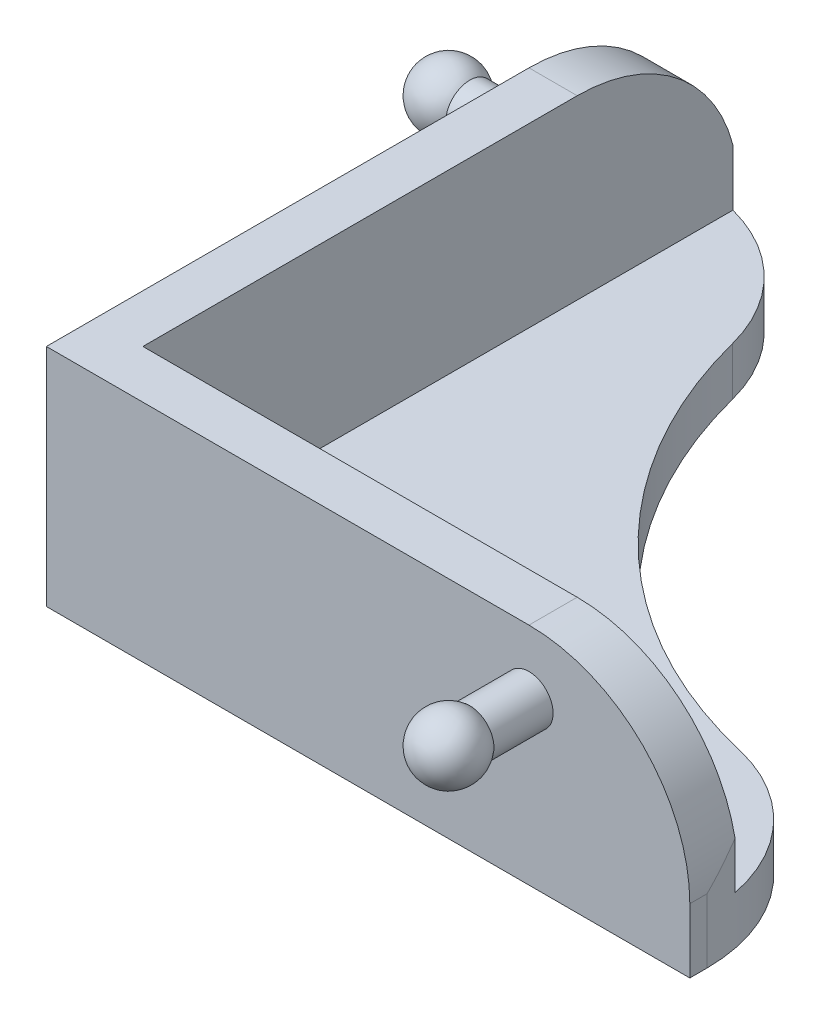
SolidWorks part; units mm, degrees
note: The reader was unsure of these and kept them because the rebuilt part matched: shared geometry of "Sketch1<4>".
ref_plane "Front Plane" through (0, 0, 0) normal (0, 0, 1) x (1, 0, 0)
ref_plane "Top Plane" through (0, 0, 0) normal (0, 1, 0) x (1, 0, 0)
ref_plane "Right Plane" through (0, 0, 0) normal (1, 0, 0) x (0, 0, -1)
sketch "Sketch1" plane through (0, 0, 0) normal (0, 1, 0) x (1, 0, 0)
  line L0 (-13.8131, -7.4977) -> (-13.8131, 29.1799)
  line L1 (-16.8131, 29.5023) -> (-16.3316, 29.5023)
  line L2 (-16.8131, 29.5023) -> (-16.8131, -10.4977)
  line L3 (-16.8131, -10.4977) -> (23.1869, -10.4977)
  line L4 (23.1869, -9.4227) -> (23.1869, -10.4977)
  line L5 (-13.8131, -7.4977) -> (22.9999, -7.4977)
  arc A0 (-6.6492, 22.0023) -> (15.4897, 0.3085) centre (22.3982, 29.5023) ccw
  arc A1 (15.4897, 0.3085) -> (23.1869, -9.4227) centre (13.1869, -9.4227) cw
  arc A2 (-6.6492, 22.0023) -> (-16.3316, 29.5023) centre (-16.3316, 19.5023) ccw
  dimension "D3" = 30
  dimension "D4" = 10
  dimension "D1" = 40
  dimension "D2" = 40
  dimension "D5" = 3
  dimension "D6" = 3
extrude "Boss-Extrude2" add sketch "Sketch1" along normal blind 3 contours A0 A2 L0 L5 A1 | L0 A2 L1 L2 L3 L4 A1 L5
extrude "Boss-Extrude3" add sketch "Sketch1<4>" along normal blind 14 contours L0 A2 L1 L2 L3 L4 A1 L5
sketch "Sketch1<4>" plane through (0, 0, 0) normal (0, 1, 0) x (1, 0, 0) same geometry as "Sketch1"
fillet "Fillet2" radius 10 2 edges at (-16.5724, 14, -29.5023) (23.1869, 14, 9.9602)
sketch "Sketch2" plane through (0, 0, 10.4977) normal (0, 0, 1) x (1, 0, 0)
  line L0 (-16.8131, 14) -> (-16.8131, 0) construction
  line L1 (22, 0) -> (-22, 0) construction
  circle A0 centre (13.1869, 10) radius 1.5
  point P4 (0, 0)
  dimension "D3" = 3
  dimension "D1" = 30
  dimension "D2" = 10
sketch "Sketch3" plane through (-16.8131, 0, 0) normal (-1, 0, 0) x (0, 0, 1)
  line L0 (10.4977, 14) -> (10.4977, 0) construction
  line L1 (22, 0) -> (-22, 0) construction
  circle A0 centre (-19.5023, 10) radius 1.5
  point P4 (0, 0)
  dimension "D3" = 3
  dimension "D1" = 30
  dimension "D2" = 10
extrude "Boss-Extrude4" add sketch "Sketch3" along normal blind 5
sketch "Sketch4" plane through (-21.8131, 0, 0) normal (-1, 0, 0) x (0, 0, 1)
  line L0 (-19.5023, 12) -> (-19.5023, 8)
  arc A0 (-19.5023, 12) -> (-19.5023, 8) centre (-19.5023, 10) ccw
  dimension "D1" = 2
revolve "Revolve1" add sketch "Sketch4" angle 360 about L0
extrude "Boss-Extrude5" add sketch "Sketch2" along normal blind 5
sketch "Sketch5" plane through (0, 0, 15.4977) normal (0, 0, 1) x (1, 0, 0)
  line L0 (13.1869, 12) -> (13.1869, 8)
  arc A0 (13.1869, 12) -> (13.1869, 8) centre (13.1869, 10) ccw
  dimension "D1" = 2
revolve "Revolve2" add sketch "Sketch5" angle 360 about L0
